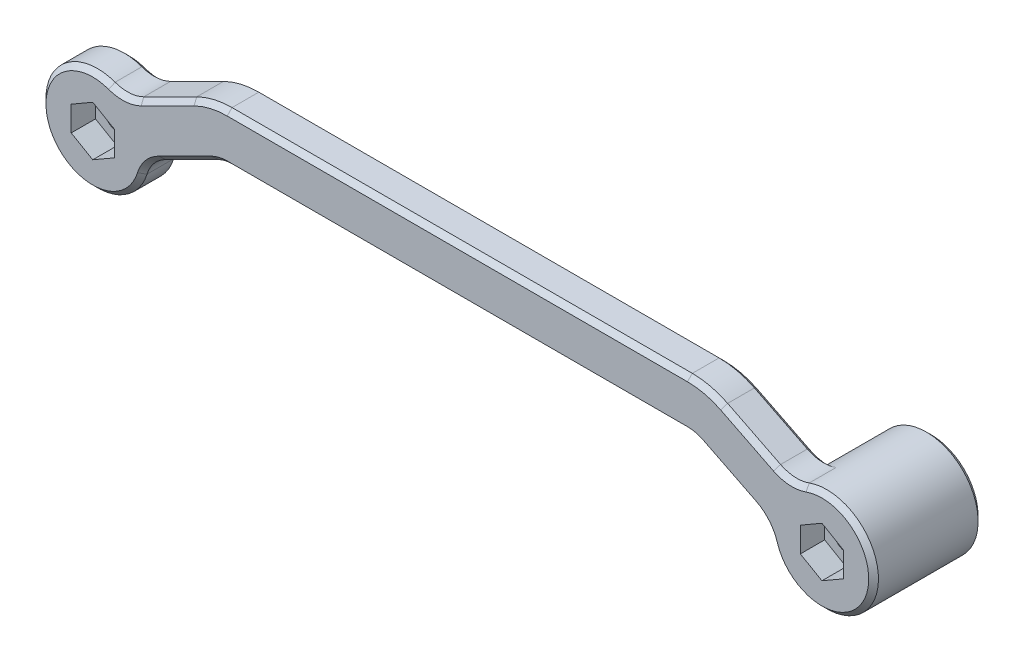
SolidWorks part; units mm, degrees
ref_plane "Front Plane" through (0, 0, 0) normal (0, 0, 1) x (1, 0, 0)
ref_plane "Top Plane" through (0, 0, 0) normal (0, 1, 0) x (1, 0, 0)
ref_plane "Right Plane" through (0, 0, 0) normal (1, 0, 0) x (0, 0, -1)
sketch "Sketch1" plane through (0, 0, 0) normal (0, 0, 1) x (1, 0, 0)
  line L0 (-60, 0) -> (60, 0) construction
  line L1 (-60, 0) -> (-40, 10) construction
  line L2 (-40, 10) -> (40, 10) construction
  line L3 (40, 10) -> (60, 0) construction
  line L4 (-40.9443, 14) -> (40.9443, 14) construction
  line L5 (40.9443, 14) -> (61.7889, 3.5777) construction
  line L6 (-61.7889, 3.5777) -> (-40.9443, 14) construction
  line L7 (-52.3974, 8.2735) -> (-43.6892, 12.6276)
  line L8 (-37.8754, 14) -> (37.8754, 14)
  line L9 (43.6892, 12.6276) -> (52.3974, 8.2735)
  line L10 (43.6892, 12.6276) -> (61.7889, 3.5777) construction
  line L11 (-37.8754, 6) -> (37.8754, 6)
  line L12 (40.1115, 5.4721) -> (48.8197, 1.118)
  line L13 (-61.7889, 3.5777) -> (-43.6892, 12.6276) construction
  line L14 (-48.8197, 1.118) -> (-40.1115, 5.4721)
  line L15 (-58.2111, -3.5777) -> (-40.1115, 5.4721) construction
  line L17 (40.1115, 5.4721) -> (58.2111, -3.5777) construction
  circle A0 centre (-60, 0) radius 2.05
  circle A1 centre (60, 0) radius 2.05
  arc A2 (-57.1162, 7.9959) -> (-51.873, -2.4905) centre (-60, 0) ccw
  arc A3 (51.873, -2.4905) -> (57.1162, 7.9959) centre (60, 0) ccw
  arc A4 (37.8754, 14) -> (43.6892, 12.6276) centre (37.8754, 1) cw
  arc A5 (-43.6892, 12.6276) -> (-37.8754, 14) centre (-37.8754, 1) cw
  arc A6 (-40.1115, 5.4721) -> (-37.8754, 6) centre (-37.8754, 1) cw
  arc A7 (37.8754, 6) -> (40.1115, 5.4721) centre (37.8754, 1) cw
  arc A8 (-52.3974, 8.2735) -> (-57.1162, 7.9959) centre (-55.0807, 13.64) cw
  arc A9 (52.3974, 8.2735) -> (57.1162, 7.9959) centre (55.0807, 13.64) ccw
  arc A10 (48.8197, 1.118) -> (51.873, -2.4905) centre (46.1364, -4.2485) cw
  arc A11 (-51.873, -2.4905) -> (-48.8197, 1.118) centre (-46.1364, -4.2485) cw
  point P4 (0, 0)
  point P9 (0, 10)
  dimension "D1" = 4.1
  dimension "D2" = 4.1
  dimension "D3" = 17
  dimension "D4" = 17
  dimension "D8" = 13
  dimension "D11" = 6
  dimension "D12" = 8
  dimension "D10" = 6
  dimension "D5" = 120
  dimension "D6" = 80
  dimension "D7" = 10
  dimension "D9" = 4
extrude "Boss-Extrude1" add sketch "Sketch1" along normal blind 6
sketch "Sketch3" plane through (0, 0, 6) normal (0, 0, 1) x (1, 0, 0)
  line L1 (-60, 4.0992) -> (-63.55, 2.0496)
  line L2 (-63.55, 2.0496) -> (-63.55, -2.0496)
  line L3 (-63.55, -2.0496) -> (-60, -4.0992)
  line L4 (-60, -4.0992) -> (-56.45, -2.0496)
  line L5 (-56.45, -2.0496) -> (-56.45, 2.0496)
  line L6 (-56.45, 2.0496) -> (-60, 4.0992)
  line L7 (60, 4.0992) -> (56.45, 2.0496)
  line L8 (56.45, 2.0496) -> (56.45, -2.0496)
  line L9 (56.45, -2.0496) -> (60, -4.0992)
  line L10 (60, -4.0992) -> (63.55, -2.0496)
  line L11 (63.55, -2.0496) -> (63.55, 2.0496)
  line L12 (63.55, 2.0496) -> (60, 4.0992)
  circle A2 centre (-60, 0) radius 3.55 construction
  circle A3 centre (60, 0) radius 3.55 construction
  dimension "D1" = 7.1
  dimension "D2" = 7.1
extrude "Cut-Extrude1" cut sketch "Sketch3" against normal blind 4
sketch "Sketch4" plane through (0, 0, 0) normal (0, 0, -1) x (-1, 0, 0)
  circle A0 centre (-60, 0) radius 2.05
  circle A1 centre (-60, 0) radius 8.5
extrude "Boss-Extrude2" add sketch "Sketch4" along normal blind 12 and the other way blind 1
chamfer "Chamfer3" distance 0.8 angle 45 33 edges at (39.0242, 5.8662, 0) (44.4656, 3.2951, 0) (0, 6, 0) (50.7167, -0.3729, 0) (-39.0242, 5.8662, 0) (52.3974, 3.8013, 0) (-44.4656, 3.2951, 0) (54.7283, 7.6504, 0) (-50.7167, -0.3729, 0) (48.0433, 10.4505, 0) (-67.6026, -3.8013, 0) (40.8622, 13.6522, 0) (-54.7283, 7.6504, 0) (0, 14, 0) (-48.0433, 10.4505, 0) (-40.8622, 13.6522, 0) (39.0242, 5.8662, 6) (44.4656, 3.2951, 6) (0, 6, 6) (50.7167, -0.3729, 6) (-39.0242, 5.8662, 6) (67.6026, -3.8013, 6) (-44.4656, 3.2951, 6) (54.7283, 7.6504, 6) (-50.7167, -0.3729, 6) (48.0433, 10.4505, 6) (-67.6026, -3.8013, 6) (40.8622, 13.6522, 6) (-54.7283, 7.6504, 6) (0, 14, 6) (-48.0433, 10.4505, 6) (-40.8622, 13.6522, 6) (51.5, 0, -12)
